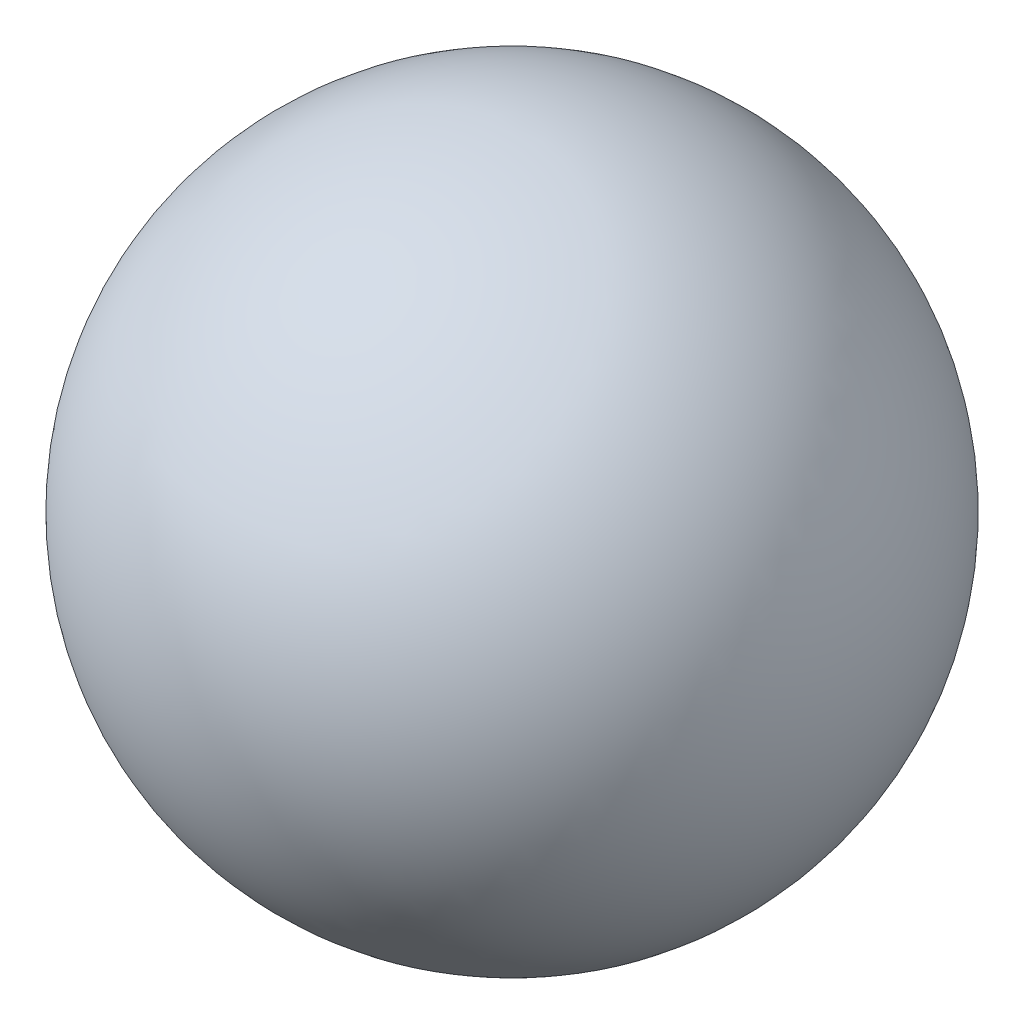
SolidWorks part; units mm, degrees
ref_plane "Front" through (0, 0, 0) normal (0, 0, 1) x (1, 0, 0)
ref_plane "Top" through (0, 0, 0) normal (0, 1, 0) x (1, 0, 0)
ref_plane "Right" through (0, 0, 0) normal (1, 0, 0) x (0, 0, -1)
sketch "Sketch1" plane through (0, 0, 0) normal (0, 0, 1) x (1, 0, 0)
  line L0 (0, 7) -> (0, -7)
  line L1 (0, 8) -> (0, 7)
  line L2 (0, -7) -> (0, -8)
  arc A0 (0, 7) -> (0, -7) centre (0, 0) cw
  arc A1 (0, -8) -> (0, 8) centre (0, 0) ccw
  dimension "D1" = 8
  dimension "D2" = 1
revolve "Core" add sketch "Sketch1" angle 360 about L0 region at (2.9709, 0, 0)
revolve "Coating" add sketch "Sketch1<3>" angle 360 about L0 region at (0.1789, 7.5, 0)
sketch "Sketch1<3>" plane through (0, 0, 0) normal (0, 0, 1) x (1, 0, 0) same geometry as "Sketch1"
